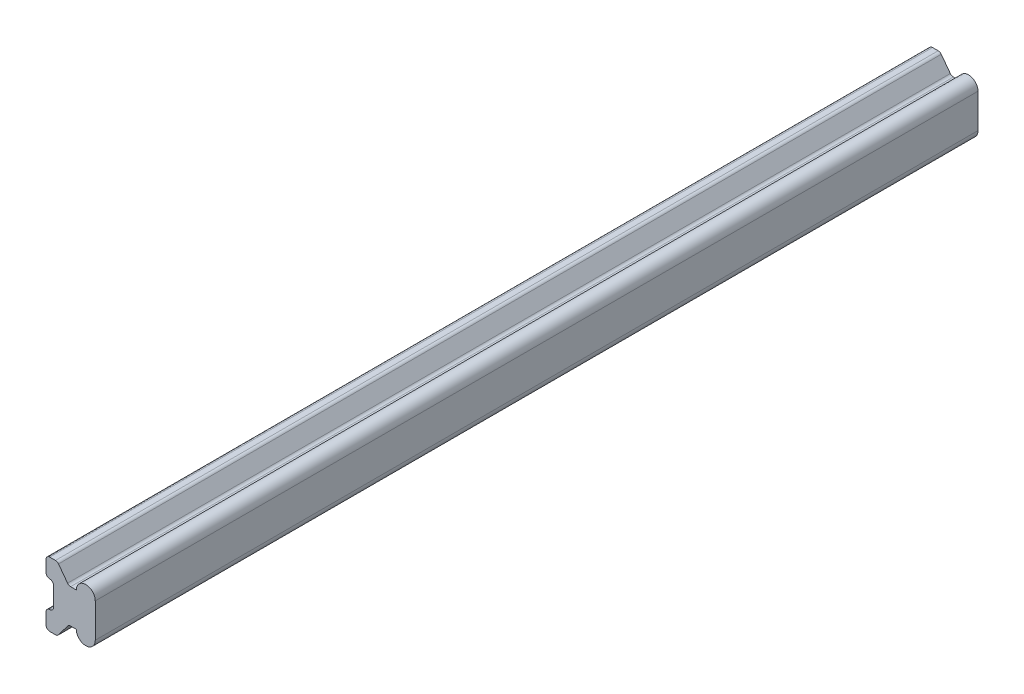
SolidWorks part; units mm, degrees
ref_plane "Front Plane" through (0, 0, 0) normal (0, 0, 1) x (1, 0, 0)
ref_plane "Top Plane" through (0, 0, 0) normal (0, 1, 0) x (1, 0, 0)
ref_plane "Right Plane" through (0, 0, 0) normal (1, 0, 0) x (0, 0, -1)
sketch "Sketch1" plane through (0, 0, 0) normal (0, 0, 1) x (1, 0, 0)
  line L0 (0, 0) -> (0, 3.5)
  line L1 (0, 3.5) -> (-2, 3.5)
  line L2 (-2, 3.5) -> (-2, 8.5)
  line L3 (0, 0) -> (0, -3.5)
  line L4 (0, -3.5) -> (-2, -3.5)
  line L5 (-2, -3.5) -> (-2, -8.5)
  line L6 (-2, 8.5) -> (1, 8.5)
  line L7 (4, 4.5) -> (6, 4.5)
  line L9 (4, 4.5) -> (1, 8.5)
  line L10 (11, 0) -> (11, 4.5)
  line L11 (11, 0) -> (11, -4.5)
  line L12 (1, -8.5) -> (-2, -8.5)
  line L14 (6, -4.5) -> (4, -4.5)
  line L15 (1, -8.5) -> (4, -4.5)
  arc A0 (11, 4.5) -> (6, 4.5) centre (8.5, 4.5) ccw
  arc A1 (6, -4.5) -> (11, -4.5) centre (8.5, -4.5) ccw
extrude "Boss-Extrude1" add sketch "Sketch1" along normal blind 233
fillet "Fillet1" radius 1 10 edges at (4, -4.5, 116.5) (1, -8.5, 116.5) (-2, -8.5, 116.5) (-2, -3.5, 116.5) (0, -3.5, 116.5) (0, 3.5, 116.5) (-2, 3.5, 116.5) (-2, 8.5, 116.5) (1, 8.5, 116.5) (4, 4.5, 116.5)
